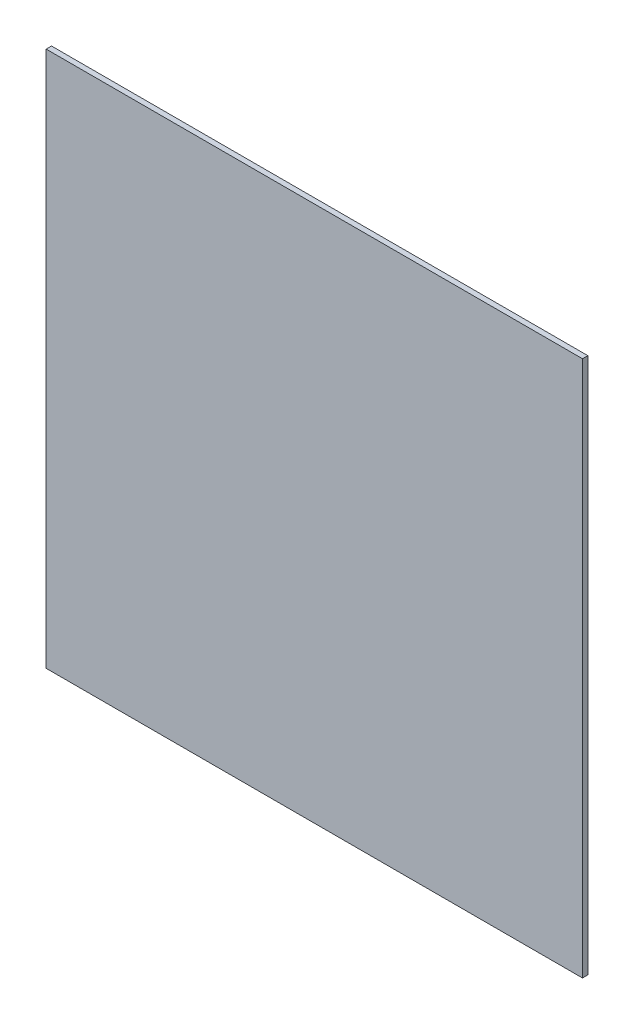
SolidWorks part; units mm, degrees
ref_plane "Front Plane" through (0, 0, 0) normal (0, 0, 1) x (1, 0, 0)
ref_plane "Top Plane" through (0, 0, 0) normal (0, 1, 0) x (1, 0, 0)
ref_plane "Right Plane" through (0, 0, 0) normal (1, 0, 0) x (0, 0, -1)
sketch "Sketch1" plane through (0, 0, 0) normal (0, 0, 1) x (1, 0, 0)
  line L1 (-10000, 10000) -> (10000, 10000)
  line L2 (-10000, 10000) -> (-10000, -10000)
  line L3 (-10000, -10000) -> (10000, -10000)
  line L4 (10000, 10000) -> (10000, -10000)
  line L5 (-10000, 10000) -> (10000, -10000) construction
  line L6 (-10000, -10000) -> (10000, 10000) construction
  point P0 (0, 0)
  dimension "D1" = 20000
  dimension "D2" = 20000
extrude "Boss-Extrude1" add sketch "Sketch1" against normal blind 200
